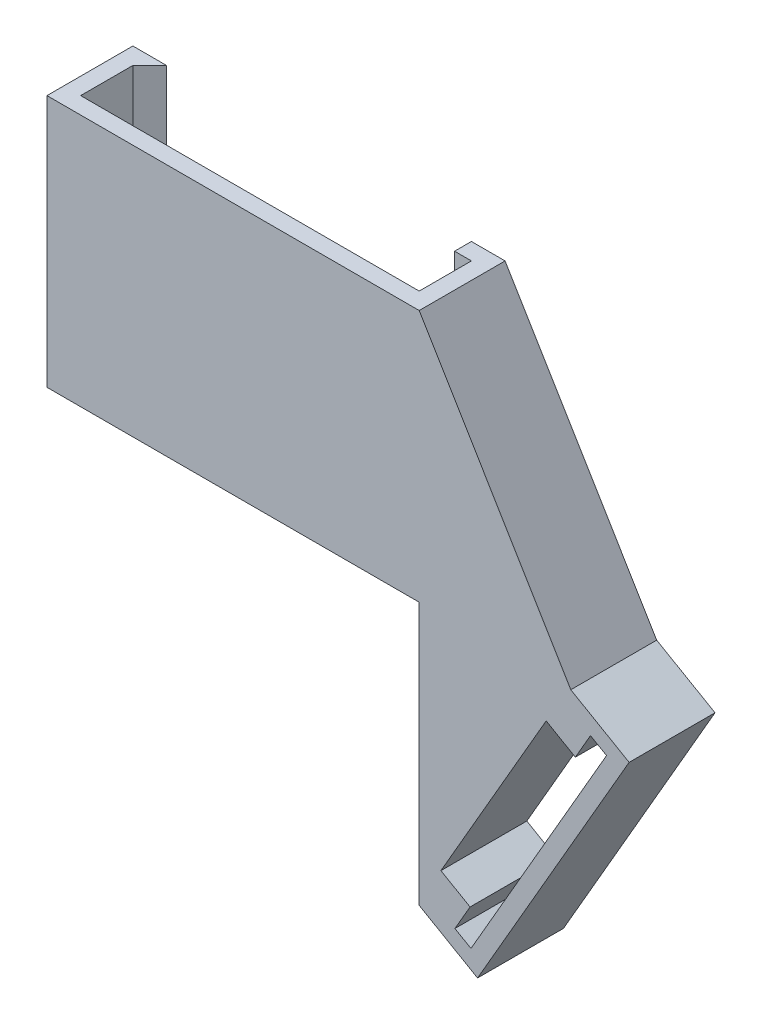
SolidWorks part; units mm, degrees
ref_plane "Front Plane" through (0, 0, 0) normal (0, 0, 1) x (1, 0, 0)
ref_plane "Top Plane" through (0, 0, 0) normal (0, 1, 0) x (1, 0, 0)
ref_plane "Right Plane" through (0, 0, 0) normal (1, 0, 0) x (0, 0, -1)
sketch "Sketch1" plane through (0, 0, 0) normal (0, 1, 0) x (1, 0, 0)
  line L0 (18.1, 3.1) -> (18.1, 5.1)
  line L1 (20.1, -3.1) -> (-20.1, -3.1)
  line L2 (20.1, -3.1) -> (20.1, 3.1)
  line L3 (20.1, 3.1) -> (18.1, 3.1)
  line L4 (-20.1, -3.1) -> (-20.1, 3.1)
  line L5 (20.1, -3.1) -> (-20.1, 3.1) construction
  line L6 (20.1, 3.1) -> (-20.1, -3.1) construction
  line L7 (18.1, 5.1) -> (22.1, 5.1)
  line L8 (22.1, 5.1) -> (22.1, -5.1)
  line L9 (22.1, -5.1) -> (-22.1, -5.1)
  line L10 (-22.1, -5.1) -> (-22.1, 5.1)
  line L11 (-22.1, 5.1) -> (-18.1, 5.1)
  line L12 (-18.1, 5.1) -> (-20.1, 3.1)
  point P0 (0, 0)
  dimension "D1" = 40.2
  dimension "D2" = 6.2
  dimension "D3" = 2
  dimension "D4" = 2
  dimension "D5" = 45
  dimension "D6" = 2
  dimension "D7" = 2
  dimension "D8" = 2
extrude "Boss-Extrude1" add sketch "Sketch1" along normal blind 30
sketch "Sketch2" plane through (0, 0, 5.1) normal (0, 0, 1) x (1, 0, 0)
  line L0 (47.0282, 34) -> (29.0282, 65.1769)
  line L5 (47.0282, 34) -> (40.1, 30)
  line L6 (29.0282, 65.1769) -> (22.1, 61.1769)
  line L8 (47.0282, 34) -> (22.1, 61.1769) construction
  line L9 (29.0282, 65.1769) -> (40.1, 30) construction
  line L11 (40.1, 30) -> (22.1, 0)
  line L12 (22.1, 0) -> (22.1, 30)
  line L13 (40.1, 30) -> (22.1, 30) construction
  line L14 (22.1, 30) -> (22.1, 61.1769)
  point P1 (34.5641, 47.5885)
  dimension "D1" = 30
  dimension "D2" = 36
  dimension "D3" = 8
extrude "Boss-Extrude2" add sketch "Sketch2" against normal up to surface (10.2 mm away) up to face at (20.1, 15, -5.1)
sketch "Sketch3" plane through (0, 0, 5.1) normal (0, 0, 1) x (1, 0, 0)
  line L0 (44.3462, 34.6454) -> (28.2462, 62.5315)
  line L1 (44.3462, 34.6454) -> (42.4409, 33.5454)
  line L2 (28.2462, 62.5315) -> (26.3409, 61.4315)
  line L3 (42.4409, 33.5454) -> (40.6409, 36.6631)
  line L4 (44.3462, 34.6454) -> (26.3409, 61.4315) construction
  line L5 (28.2462, 62.5315) -> (42.4409, 33.5454) construction
  line L6 (47.0282, 34) -> (29.0282, 65.1769) construction
  line L7 (35.3435, 48.0385) -> (38.0282, 49.5885) construction
  line L9 (28.1409, 58.3138) -> (24.6768, 56.3138)
  line L10 (40.6409, 36.6631) -> (37.1768, 34.6631)
  line L11 (24.6768, 56.3138) -> (37.1768, 34.6631)
  line L12 (28.1409, 58.3138) -> (26.3409, 61.4315)
  line L13 (35.3435, 48.0385) -> (30.9268, 45.4885) construction
  point P1 (35.3435, 48.0385)
  dimension "D1" = 2
  dimension "D2" = 2.2
  dimension "D3" = 32.2
  dimension "D4" = 25
  dimension "D5" = 4
extrude "Cut-Extrude1" cut sketch "Sketch3" against normal up to surface (10.2 mm away) up to face at (27.3321, 31.2942, -5.1)
ref_plane "Plane1" [suppressed] through (29.0282, 0, 0) normal (1, 0, 0) x (0, 0, -1)
sketch "Sketch5" [suppressed] plane through (29.0282, 0, 0) normal (1, 0, 0) x (0, 0, -1)
  line L0 (-5.1, 65.1769) -> (-5.1, 73.1769)
  line L1 (5.1, 73.1769) -> (5.1, 65.1769)
  line L2 (-5.1, 65.1769) -> (5.1, 65.1769)
  arc A0 (5.1, 73.1769) -> (-5.1, 73.1769) centre (0, 73.1769) ccw
  circle A1 centre (0, 73.1769) radius 3.1
  dimension "D1" = 6.2
  dimension "D2" = 8
extrude "Boss-Extrude4" [suppressed] add sketch "Sketch5" against normal blind 4 separate body
sketch "Sketch6" [suppressed] plane through (0, 0, 5.1) normal (0, 0, 1) x (1, 0, 0)
  line L0 (29.0282, 65.1769) -> (25.0282, 62.8675)
  line L1 (47.0282, 34) -> (29.0282, 65.1769) construction
  line L2 (29.0282, 65.1769) -> (22.1, 61.1769) construction
  line L3 (25.0282, 62.8675) -> (25.0282, 65.1769)
  line L4 (25.0282, 65.1769) -> (29.0282, 65.1769)
extrude "Boss-Extrude5" [suppressed] add sketch "Sketch6" against normal up to surface (10.2 mm away) up to face at (34.0012, 47.2635, -5.1)
mirror "Mirror1" about plane through (0, 0, 0) normal (0, 1, 0) of bodies 103
delete or keep bodies "Body-Delete/Keep 1" type delete bodies bodies 103
